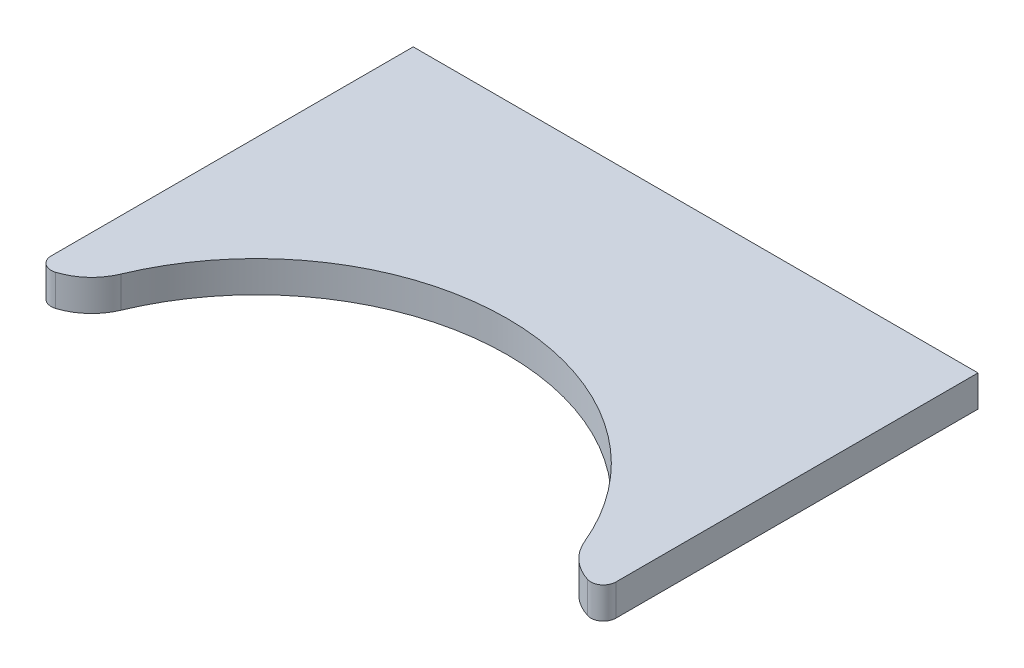
SolidWorks part; units mm, degrees
ref_plane "Front Plane" through (0, 0, 0) normal (0, 0, 1) x (1, 0, 0)
ref_plane "Top Plane" through (0, 0, 0) normal (0, 1, 0) x (1, 0, 0)
ref_plane "Right Plane" through (0, 0, 0) normal (1, 0, 0) x (0, 0, -1)
sketch "Sketch1" plane through (0, 0, 0) normal (0, 1, 0) x (1, 0, 0)
  line L1 (-28.575, 19.05) -> (28.575, 19.05)
  line L2 (-28.575, 19.05) -> (-28.575, -19.05)
  line L3 (-28.575, -19.05) -> (28.575, -19.05)
  line L4 (28.575, 19.05) -> (28.575, -19.05)
  line L5 (-28.575, 19.05) -> (28.575, -19.05) construction
  line L6 (-28.575, -19.05) -> (28.575, 19.05) construction
  point P0 (0, 0)
  dimension "D1" = 57.15
  dimension "D2" = 38.1
extrude "Boss-Extrude1" add sketch "Sketch1" along normal blind 3.175
sketch "Sketch2" plane through (0, 3.175, 0) normal (0, 1, 0) x (1, 0, 0)
  line L2 (-28.575, -19.05) -> (28.575, -19.05) construction
  line L3 (-28.575, -19.05) -> (28.575, -19.05)
  line L5 (28.575, -19.05) -> (28.575, 19.05) construction
  arc A0 (-23.4462, -15.6308) -> (23.4462, -15.6308) centre (0, -25.4) cw
  arc A1 (-28.575, -19.05) -> (-23.4462, -15.6308) centre (-28.575, -13.4938) ccw
  arc A2 (23.4462, -15.6308) -> (28.575, -19.05) centre (28.575, -13.4937) ccw
  dimension "D1" = 25.4
  dimension "D2" = 6.35
fillet "Fillet1" [suppressed] radius 6.35
fillet "Fillet2" [suppressed] radius 3.175
extrude "Cut-Extrude1" cut sketch "Sketch2" against normal through all
fillet "Fillet3" radius 1.27 2 edges at (28.575, 1.5875, 19.05) (-28.575, 1.5875, 19.05)
